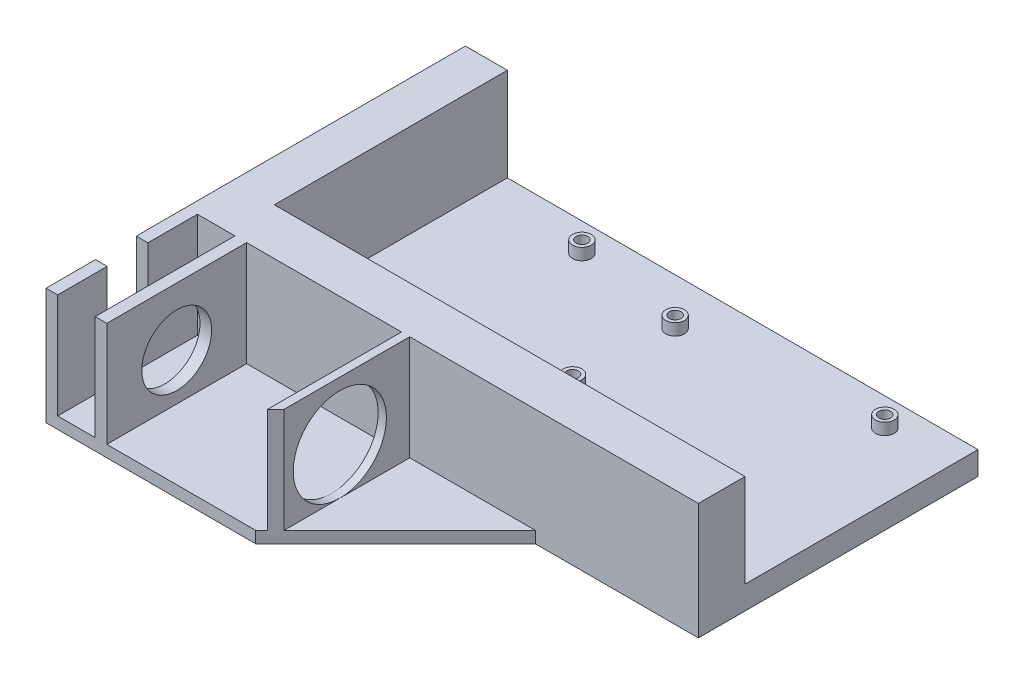
SolidWorks part; units mm, degrees
ref_plane "Front Plane" through (0, 0, 0) normal (0, 0, 1) x (1, 0, 0)
ref_plane "Top Plane" through (0, 0, 0) normal (0, 1, 0) x (1, 0, 0)
ref_plane "Right Plane" through (0, 0, 0) normal (1, 0, 0) x (0, 0, -1)
sketch "Sketch1" plane through (0, 0, 0) normal (0, 1, 0) x (1, 0, 0)
  line L0 (-69.85, -38.1) -> (69.85, -38.1)
  line L1 (-69.85, -38.1) -> (-69.85, 38.1)
  line L2 (69.85, -38.1) -> (69.85, 38.1)
  line L3 (-69.85, 38.1) -> (69.85, 38.1)
  line L4 (-69.85, -38.1) -> (69.85, 38.1) construction
  line L5 (69.85, -38.1) -> (-69.85, 38.1) construction
  line L10 (-58.42, -26.67) -> (58.42, 26.67) construction
  line L11 (58.42, -26.67) -> (-58.42, 26.67) construction
  point P1 (0, 0)
  point P2 (0, 0)
  dimension "D1" = 76.2
  dimension "D2" = 139.7
extrude "Boss-Extrude1" add sketch "Sketch1" along normal blind 31.75
sketch "Sketch2" plane through (0, 31.75, 0) normal (0, 1, 0) x (1, 0, 0)
  line L0 (-58.42, -25.4) -> (69.85, -25.4)
  line L1 (-58.42, -25.4) -> (-58.42, 38.1459)
  line L2 (69.85, -25.4) -> (69.85, 38.1459)
  line L3 (-58.42, 38.1459) -> (69.85, 38.1459)
  line L4 (69.85, -38.1) -> (69.85, 38.1) construction
  line L5 (-69.85, 38.1) -> (-69.85, -38.1) construction
  line L9 (-69.85, -38.1) -> (69.85, -38.1) construction
  dimension "D1" = 11.43
  dimension "D2" = 12.7
extrude "Cut-Extrude1" cut sketch "Sketch2" against normal blind 25.4
sketch "Sketch3" plane through (0, 6.35, 0) normal (0, 1, 0) x (1, 0, 0)
  line L0 (-58.42, -25.4) -> (-48.26, -25.4)
  line L1 (-58.42, -25.4) -> (-58.42, -15.24)
  line L2 (-48.26, -25.4) -> (-48.26, -15.24)
  line L3 (-58.42, -15.24) -> (-48.26, -15.24)
  line L4 (-58.42, -25.4) -> (69.85, -25.4) construction
  dimension "D1" = 10.16
  dimension "D2" = 10.16
extrude "Boss-Extrude3" add sketch "Sketch3" along normal blind 12.7
sketch "Sketch4" plane through (0, 19.05, 0) normal (0, 1, 0) x (1, 0, 0)
  line L0 (-48.26, -25.4) -> (-48.26, -15.24) construction
  line L1 (-48.26, -15.24) -> (-58.42, -15.24) construction
  circle A0 centre (-53.34, -20.32) radius 2.032
  point P4 (-48.26, -20.32)
  dimension "D1" = 4.064
  dimension "D2" = 5.08
  dimension "D3" = 5.08
extrude "Cut-Extrude2" cut sketch "Sketch4" against normal through all
sketch "Sketch5" plane through (0, 19.05, 0) normal (0, 1, 0) x (1, 0, 0)
  circle A0 centre (-53.34, -20.32) radius 3.937
extrude "Cut-Extrude3" cut sketch "Sketch5" against normal blind 2.286
sketch "Sketch7" plane through (0, 6.35, 0) normal (0, 1, 0) x (1, 0, 0)
  line L1 (-58.42, 38.1) -> (69.85, 38.1) construction
  circle A0 centre (-30.48, 30.48) radius 1.6002
  circle A1 centre (-24.13, -17.78) radius 1.6002
  circle A2 centre (0, -2.54) radius 1.6002
  circle A3 centre (0, 25.4) radius 1.6002
  circle A4 centre (52.07, 30.48) radius 1.6002
  circle A5 centre (50.8, -17.78) radius 1.6002
  circle A6 centre (-30.48, 30.48) radius 2.54
  circle A7 centre (-24.13, -17.78) radius 2.54
  circle A8 centre (0, 25.4) radius 2.54
  circle A9 centre (0, -2.54) radius 2.54
  circle A10 centre (50.8, -17.78) radius 2.54
  circle A11 centre (52.07, 30.48) radius 2.54
  point P15 (0, 0)
  point P20 (0, 25.4)
  dimension "D1" = 3.2004
  dimension "D10" = 5.08
  dimension "D2" = 6.35
  dimension "D3" = 48.26
  dimension "D4" = 30.48
  dimension "D5" = 5.08
  dimension "D6" = 27.94
  dimension "D7" = 74.93
  dimension "D8" = 82.55
  dimension "D9" = 7.62
extrude "Boss-Extrude5" add sketch "Sketch7" along normal blind 3.175
sketch "Sketch8" plane through (0, 0, 0) normal (0, -1, 0) x (1, 0, 0)
  line L0 (-69.85, 38.1) -> (-69.85, 76.2)
  line L1 (-69.85, 76.2) -> (-12.7, 76.2)
  line L2 (-12.7, 76.2) -> (25.4, 38.1)
  line L3 (-69.85, 38.1) -> (69.85, 38.1) construction
  line L4 (25.4, 38.1) -> (-69.85, 38.1)
  dimension "D1" = 95.25
  dimension "D2" = 57.15
  dimension "D3" = 38.1
extrude "Boss-Extrude6" add sketch "Sketch8" against normal blind 3.175
sketch "Sketch9" plane through (0, 3.175, 0) normal (0, 1, 0) x (1, 0, 0)
  line L0 (-69.85, -38.1) -> (25.4, -38.1) construction
  line L1 (-69.85, -76.2) -> (-66.675, -76.2)
  line L2 (-69.85, -76.2) -> (-69.85, -38.1)
  line L3 (-69.85, -38.1) -> (-66.675, -38.1)
  line L4 (-66.675, -76.2) -> (-66.675, -38.1)
  line L5 (-12.7, -76.2) -> (-69.85, -76.2) construction
  line L6 (-8.8265, -72.3265) -> (-11.0716, -74.5716)
  line L7 (-8.8265, -72.3265) -> (-8.8265, -38.1)
  line L8 (-8.8265, -38.1) -> (-11.0716, -38.1)
  line L9 (-11.0716, -74.5716) -> (-11.0716, -38.1)
  line L10 (-56.4515, -76.2) -> (-53.2765, -76.2)
  line L11 (-56.4515, -76.2) -> (-56.4515, -38.1)
  line L12 (-56.4515, -38.1) -> (-53.2765, -38.1)
  line L13 (-53.2765, -76.2) -> (-53.2765, -38.1)
  line L14 (25.4, -38.1) -> (-12.7, -76.2) construction
  dimension "D1" = 3.175
  dimension "D2" = 13.3985
  dimension "D3" = 44.45
extrude "Boss-Extrude7" add sketch "Sketch9" along normal up to surface (28.575 mm away) up to face at (-19.4733, 31.75, 8.4667)
sketch "Sketch10" plane through (-69.85, 0, 0) normal (-1, 0, 0) x (0, 0, 1)
  line L0 (76.2, 31.75) -> (76.2, 0) construction
  line L3 (-38.1, 0) -> (76.2, 0) construction
  circle A0 centre (57.15, 15.875) radius 5.5499
  dimension "D1" = 11.0998
  dimension "D2" = 19.05
  dimension "D3" = 15.875
extrude "Cut-Extrude4" cut sketch "Sketch10" against normal blind 3.175
sketch "Sketch11" plane through (-56.4515, 0, 0) normal (-1, 0, 0) x (0, 0, 1)
  line L2 (-38.1, 0) -> (76.2, 0) construction
  line L3 (76.2, 31.75) -> (76.2, 0) construction
  circle A0 centre (57.15, 15.875) radius 9.525
  dimension "D1" = 19.05
  dimension "D2" = 15.875
  dimension "D3" = 19.05
extrude "Cut-Extrude5" cut sketch "Sketch11" against normal blind 3.175
sketch "Sketch12" plane through (-11.0716, 0, 0) normal (-1, 0, 0) x (0, 0, 1)
  line L5 (38.1, 31.75) -> (38.1, 3.175) construction
  line L6 (-38.1, 0) -> (76.2, 0) construction
  circle A0 centre (57.15, 15.875) radius 12.7
  dimension "D1" = 25.4
  dimension "D2" = 19.05
  dimension "D3" = 15.875
extrude "Cut-Extrude6" cut sketch "Sketch12" against normal blind 3.175
sketch "Sketch13" plane through (-69.85, 0, 0) normal (-1, 0, 0) x (0, 0, 1)
  line L0 (51.6001, 15.875) -> (51.6001, 31.75)
  line L1 (-38.1, 31.75) -> (76.2, 31.75) construction
  line L2 (51.6001, 31.75) -> (62.6999, 31.75)
  line L3 (62.6999, 31.75) -> (62.6999, 15.875)
  line L4 (62.6999, 15.875) -> (51.6001, 15.875)
  circle A0 centre (57.15, 15.875) radius 5.5499 construction
  dimension "D1" = 11.0998
extrude "Cut-Extrude7" cut sketch "Sketch13" against normal blind 3.175
